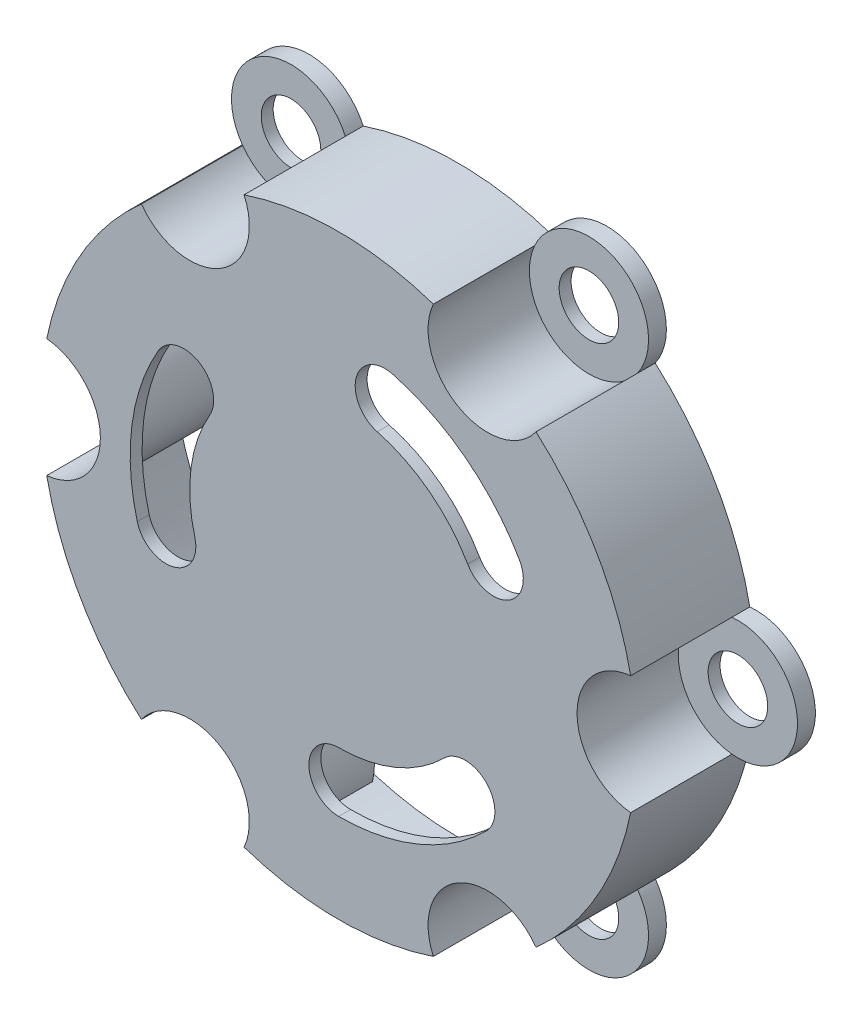
SolidWorks part; units mm, degrees
ref_plane "Front Plane" through (0, 0, 0) normal (0, 0, 1) x (1, 0, 0)
ref_plane "Top Plane" through (0, 0, 0) normal (0, 1, 0) x (1, 0, 0)
ref_plane "Right Plane" through (0, 0, 0) normal (1, 0, 0) x (0, 0, -1)
sketch "Sketch1" plane through (0, 0, 0) normal (0, 0, 1) x (1, 0, 0)
  line L0 (0, 0) -> (25.9808, 15) construction
  line L1 (0, 0) -> (7.7646, 28.9778) construction
  arc A0 (-49, -9.9499) -> (-33.1168, -37.4603) centre (0, 0) ccw
  arc A1 (49, -9.9499) -> (49, 9.9499) centre (50, 0) ccw construction
  arc A2 (15.8832, -47.4102) -> (33.1168, -37.4603) centre (25, -43.3013) ccw construction
  arc A3 (-33.1168, -37.4603) -> (-15.8832, -47.4102) centre (-25, -43.3013) ccw construction
  arc A4 (-49, 9.9499) -> (-49, -9.9499) centre (-50, 0) ccw construction
  arc A5 (-15.8832, 47.4102) -> (-33.1168, 37.4603) centre (-25, 43.3013) ccw construction
  arc A6 (33.1168, 37.4603) -> (15.8832, 47.4102) centre (25, 43.3013) ccw construction
  arc A7 (-33.1168, 37.4603) -> (-49, 9.9499) centre (0, 0) ccw
  arc A8 (15.8832, 47.4102) -> (-15.8832, 47.4102) centre (0, 0) ccw
  arc A9 (49, 9.9499) -> (33.1168, 37.4603) centre (0, 0) ccw
  arc A10 (33.1168, -37.4603) -> (49, -9.9499) centre (0, 0) ccw
  arc A11 (-15.8832, -47.4102) -> (15.8832, -47.4102) centre (0, 0) ccw
  arc A12 (25.9808, 15) -> (7.7646, 28.9778) centre (0, 0) ccw construction
  arc A13 (30.3109, 17.5) -> (9.0587, 33.8074) centre (0, 0) ccw
  arc A14 (21.6506, 12.5) -> (6.4705, 24.1481) centre (0, 0) ccw
  arc A15 (21.6506, 12.5) -> (30.3109, 17.5) centre (25.9808, 15) ccw
  arc A16 (9.0587, 33.8074) -> (6.4705, 24.1481) centre (7.7646, 28.9778) ccw
  circle A17 centre (50, 0) radius 5
  circle A18 centre (25, -43.3013) radius 5
  circle A19 centre (-25, -43.3013) radius 5
  circle A20 centre (-50, 0) radius 5
  circle A21 centre (-25, 43.3013) radius 5
  circle A22 centre (25, 43.3013) radius 5
  arc A23 (0, -30) -> (21.2132, -21.2132) centre (0, 0) ccw construction
  arc A24 (0, -35) -> (24.7487, -24.7487) centre (0, 0) ccw
  arc A25 (0, -25) -> (17.6777, -17.6777) centre (0, 0) ccw
  arc A26 (0, -25) -> (0, -35) centre (0, -30) ccw
  arc A27 (24.7487, -24.7487) -> (17.6777, -17.6777) centre (21.2132, -21.2132) ccw
  arc A28 (-25.9808, 15) -> (-28.9778, -7.7646) centre (0, 0) ccw construction
  arc A29 (-30.3109, 17.5) -> (-33.8074, -9.0587) centre (0, 0) ccw
  arc A30 (-21.6506, 12.5) -> (-24.1481, -6.4705) centre (0, 0) ccw
  arc A31 (-21.6506, 12.5) -> (-30.3109, 17.5) centre (-25.9808, 15) ccw
  arc A32 (-33.8074, -9.0587) -> (-24.1481, -6.4705) centre (-28.9778, -7.7646) ccw
  circle A33 centre (50, 0) radius 10
  circle A34 centre (25, -43.3013) radius 10
  circle A35 centre (-25, -43.3013) radius 10
  circle A36 centre (-50, 0) radius 10
  circle A37 centre (-25, 43.3013) radius 10
  circle A38 centre (25, 43.3013) radius 10
  point P6 (18.2628, 23.8006)
  point P18 (0, 0)
  point P42 (0, 0)
  point P43 (11.4805, -27.7164)
  point P50 (-29.7433, 3.9158)
  point P56 (0, 0)
  point P57 (0, 0)
  point P68 (0, 0)
  dimension "D1" = 6
  dimension "D2" = 50
  dimension "D3" = 20
  dimension "D4" = 30
  dimension "D7" = 10
  dimension "D8" = 10
  dimension "D11" = 6
  dimension "D5" = 30
  dimension "D6" = 45
  dimension "D9" = 6
  dimension "D10" = 3
extrude "Boss-Extrude2" add sketch "Sketch1" along normal blind 20 contours A38 A8 A37 A7 A36 A0 A35 A11 A34 A10 A33 A9 A16 A13 A15 A14 A27 A24 A26 A25 A32 A29 A31 A30 region at (0, 0, 0)
extrude "Boss-Extrude3" add sketch "Sketch1<3>" along normal blind 3 contours A37 | A21 | A20 | A36 | A35 | A19 | A34 | A18 | A33 | A17 | A38 | A22
sketch "Sketch1<3>" plane through (0, 0, 0) normal (0, 0, 1) x (1, 0, 0) same geometry as "Sketch1"
shell "Shell1" thickness 2 removed face at (0, 0, 0) removed face at (14.6398, 19.079, 10) removed face at (5.3498, 29.6248, 10) removed face at (27.2308, 12.8349, 10) removed face at (20.4957, 26.7105, 10) removed face at (12.8841, -31.1051, 10) removed face at (22.981, -19.4454, 10) removed face at (9.203, -22.2179, 10) removed face at (-2.5, -30, 10) removed face at (-33.3799, 4.3945, 10) removed face at (-23.8428, 3.139, 10) removed face at (-24.7308, 17.1651, 10) removed face at (-28.3307, -10.1794, 10) removed face at (55, 0, 3) removed face at (30, 43.3013, 3) removed face at (-20, 43.3013, 3) removed face at (-45, 0, 3) removed face at (-20, -43.3013, 3) removed face at (30, -43.3013, 3)
